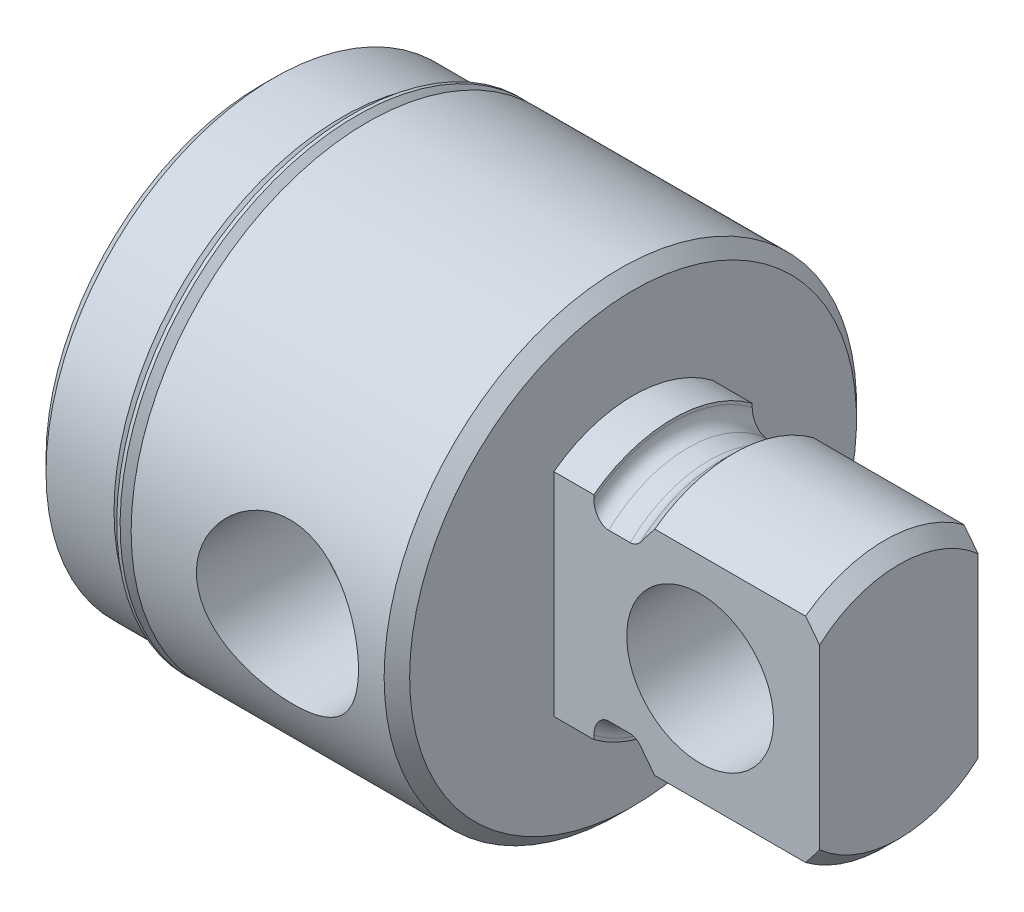
SolidWorks part; units mm, degrees
material "Cast Alloy Steel"
ref_plane "Front Plane" through (0, 0, 0) normal (0, 0, 1) x (1, 0, 0)
ref_plane "Top Plane" through (0, 0, 0) normal (0, 1, 0) x (1, 0, 0)
ref_plane "Right Plane" through (0, 0, 0) normal (1, 0, 0) x (0, 0, -1)
ref_plane "Plane1" through (38.1, 0, 0) normal (1, 0, 0) x (0, 0, -1)
sketch "Sketch1" plane through (0, 0, 0) normal (0, 0, 1) x (1, 0, 0)
  line L0 (0, 0) -> (0, 12.846)
  line L1 (0, 12.846) -> (0.762, 13.6081)
  line L2 (0.762, 13.6081) -> (4.826, 13.6081)
  line L3 (4.826, 13.6081) -> (5.588, 12.846)
  line L4 (5.588, 12.846) -> (6.35, 12.846)
  line L5 (6.35, 12.846) -> (6.35, 14.1097)
  line L6 (6.35, 14.1097) -> (21.463, 14.1097)
  line L7 (21.463, 14.1097) -> (22.225, 13.3477)
  line L8 (22.225, 13.3477) -> (22.225, 0)
  line L9 (22.225, 0) -> (0, 0)
  line L10 (22.225, 0) -> (0, 0) construction
revolve "Revolve1" add sketch "Sketch1" angle 360 about L10 reverse direction yes
sketch "Sketch2" plane through (0, 0, 0) normal (0, 0, 1) x (1, 0, 0)
  line L0 (22.225, 0) -> (22.225, 7.9057)
  line L1 (22.225, 7.9057) -> (24.6126, 7.9057)
  line L2 (24.6126, 7.9057) -> (24.6126, 7.7279)
  line L3 (25.5016, 6.8389) -> (26.7843, 6.8389)
  line L4 (27.383, 7.0708) -> (27.4129, 7.098)
  line L5 (27.4129, 7.098) -> (28.2524, 7.9375)
  line L6 (28.2524, 7.9375) -> (37.2605, 7.9375)
  line L7 (37.2605, 7.9375) -> (38.1, 7.098)
  line L8 (38.1, 7.098) -> (38.1, 0)
  line L9 (38.1, 0) -> (22.225, 0)
  line L10 (38.1, 0) -> (22.225, 0) construction
  arc A0 (24.6126, 7.7279) -> (25.5016, 6.8389) centre (25.5016, 7.7279) ccw
  arc A1 (26.7843, 6.8389) -> (27.383, 7.0708) centre (26.7843, 7.7279) ccw
revolve "Revolve2" add sketch "Sketch2" angle 360 about L10 reverse direction yes
cosmetic thread "Cosmetic Thread1" parameters "D1"=10.6871, "D2"=14.1961
sketch "Sketch3" plane through (38.1, 0, 0) normal (1, 0, 0) x (0, 0, -1)
  line L0 (-28.2194, -56.4388) -> (28.2194, -56.4388)
  line L1 (28.2194, -56.4388) -> (28.2194, 56.4388)
  line L2 (28.2194, 56.4388) -> (-28.2194, 56.4388)
  line L3 (-28.2194, 56.4388) -> (-28.2194, -56.4388)
  line L4 (-4.7307, -28.2194) -> (4.7307, -28.2194)
  line L5 (4.7307, -28.2194) -> (4.7307, 28.2194)
  line L6 (4.7307, 28.2194) -> (-4.7307, 28.2194)
  line L7 (-4.7307, 28.2194) -> (-4.7307, -28.2194)
extrude "Cut-Extrude1" cut sketch "Sketch3" against normal blind 15.875
ref_plane "Plane2" through (22.225, 0, 0) normal (1, 0, 0) x (0, 0, -1)
hole_wizard "Hole1" positions "Sketch5" profile "Sketch4" legacy
sketch "Sketch5" plane through (0, 0, 0) normal (-1, 0, 0) x (0, 0, 1)
  point P0 (0, 0)
sketch "Sketch4" plane through (0, 0, 0) normal (0, 1, 0) x (0, 0, 1)
  line L0 (0, 0) -> (0, 23.7046)
  line L1 (0, 23.7046) -> (4.7625, 20.955)
  line L2 (4.7625, 20.955) -> (4.7625, 0)
  line L4 (4.7625, 0) -> (0, 0)
  line L6 (0, 23.7046) -> (-4.7625, 20.955) construction
  line L7 (0, -4.2442) -> (0, 117.3081) construction
  dimension "Diameter" = 9.525
  dimension "Depth" = 20.955
  dimension "Drill Angle" = 120
ref_plane "Plane3" through (0, 0, 0) normal (0, 0.9998, 0.0175) x (1, 0, 0)
sketch "Sketch6" plane through (0, 0, 0) normal (0, 0.9998, 0.0175) x (1, 0, 0)
  line L0 (15.0876, 0) -> (19.7106, 0)
  line L1 (19.7106, 0) -> (19.7106, -7.1755)
  line L2 (19.7106, -7.1755) -> (19.9271, -14.1097)
  line L3 (19.9271, -14.1097) -> (15.0876, -14.1097)
  line L4 (15.0876, -14.1097) -> (15.0876, 0)
  line L5 (15.0876, -14.1097) -> (15.0876, 0) construction
revolve "Cut-Revolve1" cut sketch "Sketch6" angle 360 about L5 reverse direction yes
cosmetic thread "Cosmetic Thread2" parameters "D1"=6.9342, "D2"=10.287
ref_plane "Plane4" through (15.0876, 0, 0) normal (1, 0, 0) x (0, 0, -1)
ref_plane "Plane5" through (5.588, 0, 0) normal (1, 0, 0) x (0, 0, -1)
sketch "Sketch7" plane through (0, 0, 0) normal (0, 0, 1) x (1, 0, 0)
  line L0 (5.4861, 14.0255) -> (6.2275, 13.2842)
  line L1 (6.2275, 13.1046) -> (5.969, 12.846)
  line L2 (5.969, 12.846) -> (5.588, 12.846)
  line L3 (5.588, 12.846) -> (5.588, 12.592)
  line L4 (5.588, 12.592) -> (6.35, 12.592)
  line L5 (6.35, 12.592) -> (6.35, 13.449)
  line L6 (6.35, 13.449) -> (5.6893, 14.1097)
  line L7 (5.6893, 14.1097) -> (5.4861, 14.1097)
  line L8 (5.4861, 14.1097) -> (5.4861, 14.0255)
  line L9 (6.35, 0) -> (5.588, 0) construction
  arc A0 (6.2275, 13.2842) -> (6.2275, 13.1046) centre (6.1377, 13.1944) cw
revolve "Revolve3" add sketch "Sketch7" angle 360 about L9 reverse direction yes
ref_plane "Plane6" through (38.227, 0, 0) normal (1, 0, 0) x (0, 0, -1)
sketch "Sketch8" plane through (0, 0, 0) normal (0, 0, 1) x (1, 0, 0)
  circle A0 centre (30.9626, 0) radius 4.3878
extrude "Cut-Extrude2" cut sketch "Sketch8" along normal blind 7.0961 and the other way blind 7.0961
ref_plane "Plane7" through (24.6126, 0, 0) normal (1, 0, 0) x (0, 0, -1)
ref_plane "Plane8" through (33.3248, 0, 0) normal (1, 0, 0) x (0, 0, -1)
ref_plane "Plane9" through (30.9626, 0, 0) normal (1, 0, 0) x (0, 0, -1)
ref_plane "Plane10" through (38.1, 0, 0) normal (1, 0, 0) x (0, 0, -1)
ref_plane "Plane11" through (0, 0, 0) normal (0, 0, 1) x (1, 0, 0)
ref_plane "Plane12" through (24.6126, 0, 0) normal (1, 0, 0) x (0, 0, -1)
ref_plane "Plane13" through (0, 0, 0) normal (0, 1, 0) x (1, 0, 0)
ref_plane "Plane14" through (0, 10.2743, 0) normal (0, 1, 0) x (1, 0, 0)
ref_plane "Plane15" through (22.225, 0, 0) normal (1, 0, 0) x (0, 0, -1)
ref_plane "1 XY" through (24.6126, 0, 0) normal (1, 0, 0) x (0, 0, -1)
ref_plane "1 XZ" through (0, 0, 0) normal (0, -1, 0) x (-1, 0, 0)
ref_plane "1 YZ" through (0, 0, 0) normal (0, 0, -1) x (-1, 0, 0)
ref_axis "1 X" through (24.6126, 0, 80.9) along (0, 0, -1)
ref_axis "1 Y" through (24.6126, -50, 0) along (0, 1, 0)
ref_axis "1 Z" through (80.9, 0, 0) along (-1, 0, 0)
sketch3d "1"
  point P0 (24.6126, 0, 0)
ref_plane "c1 XY" through (0, 0, 0) normal (0, 0, 1) x (1, 0, 0)
ref_plane "c1 XZ" through (0, 7.9057, 0) normal (0, -1, 0) x (-1, 0, 0)
ref_plane "c1 YZ" through (22.225, 0, 0) normal (1, 0, 0) x (0, 0, -1)
ref_axis "c1 X" through (-80.9, 7.9057, 0) along (1, 0, 0)
ref_axis "c1 Y" through (22.225, -50, 0) along (0, 1, 0)
ref_axis "c1 Z" through (22.225, 7.9057, 80.9) along (0, 0, -1)
sketch3d "c1"
  point P0 (22.225, 7.9057, 0)
ref_plane "c2 XY" through (0, 0, 0) normal (0, 0, 1) x (1, 0, 0)
ref_plane "c2 XZ" through (0, -7.9057, 0) normal (0, -1, 0) x (-1, 0, 0)
ref_plane "c2 YZ" through (22.225, 0, 0) normal (1, 0, 0) x (0, 0, -1)
ref_axis "c2 X" through (-80.9, -7.9057, 0) along (1, 0, 0)
ref_axis "c2 Y" through (22.225, -50, 0) along (0, 1, 0)
ref_axis "c2 Z" through (22.225, -7.9057, 80.9) along (0, 0, -1)
sketch3d "c2"
  point P0 (22.225, -7.9057, 0)
ref_plane "cc1 XY" through (0, 0, 0) normal (0, 0, 1) x (1, 0, 0)
ref_plane "cc1 XZ" through (0, 0, 0) normal (0, -1, 0) x (-1, 0, 0)
ref_plane "cc1 YZ" through (22.225, 0, 0) normal (1, 0, 0) x (0, 0, -1)
ref_axis "cc1 X" through (-80.9, 0, 0) along (1, 0, 0)
ref_axis "cc1 Y" through (22.225, -50, 0) along (0, 1, 0)
ref_axis "cc1 Z" through (22.225, 0, 80.9) along (0, 0, -1)
sketch3d "cc1"
  point P0 (22.225, 0, 0)
ref_plane "cc2 XY" through (0, 0, 0) normal (0, 0, 1) x (1, 0, 0)
ref_plane "cc2 XZ" through (0, 0, 0) normal (0, -1, 0) x (-1, 0, 0)
ref_plane "cc2 YZ" through (24.6126, 0, 0) normal (1, 0, 0) x (0, 0, -1)
ref_axis "cc2 X" through (-80.9, 0, 0) along (1, 0, 0)
ref_axis "cc2 Y" through (24.6126, -50, 0) along (0, 1, 0)
ref_axis "cc2 Z" through (24.6126, 0, 80.9) along (0, 0, -1)
sketch3d "cc2"
  point P0 (24.6126, 0, 0)
ref_plane "lovra1 XY" through (33.3248, 0, 0) normal (1, 0, 0) x (0, 0, -1)
ref_plane "lovra1 XZ" through (0, 0, 0) normal (0, -1, 0) x (-1, 0, 0)
ref_plane "lovra1 YZ" through (0, 0, 0) normal (0, 0, -1) x (-1, 0, 0)
ref_axis "lovra1 X" through (33.3248, 0, 80.9) along (0, 0, -1)
ref_axis "lovra1 Y" through (33.3248, -50, 0) along (0, 1, 0)
ref_axis "lovra1 Z" through (80.9, 0, 0) along (-1, 0, 0)
sketch3d "lovra1"
  point P0 (33.3248, 0, 0)
ref_plane "lovra2 XY" through (33.3248, 0, 0) normal (1, 0, 0) x (0, 0, -1)
ref_plane "lovra2 XZ" through (0, 11.049, 0) normal (0, -1, 0) x (-1, 0, 0)
ref_plane "lovra2 YZ" through (0, 0, 0) normal (0, 0, -1) x (-1, 0, 0)
ref_axis "lovra2 X" through (33.3248, 11.049, 80.9) along (0, 0, -1)
ref_axis "lovra2 Y" through (33.3248, -50, 0) along (0, 1, 0)
ref_axis "lovra2 Z" through (80.9, 11.049, 0) along (-1, 0, 0)
sketch3d "lovra2"
  point P0 (33.3248, 11.049, 0)
ref_plane "lovra21 XY" through (0, 0, 0) normal (1, 0, 0) x (0, 0, -1)
ref_plane "lovra21 XZ" through (0, 0, 0) normal (0, -1, 0) x (-1, 0, 0)
ref_plane "lovra21 YZ" through (0, 0, 5.2705) normal (0, 0, -1) x (-1, 0, 0)
ref_axis "lovra21 X" through (0, 0, 80.9) along (0, 0, -1)
ref_axis "lovra21 Y" through (0, -50, 5.2705) along (0, 1, 0)
ref_axis "lovra21 Z" through (80.9, 0, 5.2705) along (-1, 0, 0)
sketch3d "lovra21"
  point P0 (0, 0, 5.2705)
ref_plane "lovra22 XY" through (0, 0, 0) normal (1, 0, 0) x (0, 0, -1)
ref_plane "lovra22 XZ" through (0, 0, 0) normal (0, -1, 0) x (-1, 0, 0)
ref_plane "lovra22 YZ" through (0, 0, -5.2705) normal (0, 0, -1) x (-1, 0, 0)
ref_axis "lovra22 X" through (0, 0, 80.9) along (0, 0, -1)
ref_axis "lovra22 Y" through (0, -50, -5.2705) along (0, 1, 0)
ref_axis "lovra22 Z" through (80.9, 0, -5.2705) along (-1, 0, 0)
sketch3d "lovra22"
  point P0 (0, 0, -5.2705)
ref_plane "lovra3 XY" through (33.3248, 0, 0) normal (1, 0, 0) x (0, 0, -1)
ref_plane "lovra3 XZ" through (0, -11.049, 0) normal (0, -1, 0) x (-1, 0, 0)
ref_plane "lovra3 YZ" through (0, 0, 0) normal (0, 0, -1) x (-1, 0, 0)
ref_axis "lovra3 X" through (33.3248, -11.049, 80.9) along (0, 0, -1)
ref_axis "lovra3 Y" through (33.3248, -50, 0) along (0, 1, 0)
ref_axis "lovra3 Z" through (80.9, -11.049, 0) along (-1, 0, 0)
sketch3d "lovra3"
  point P0 (33.3248, -11.049, 0)
ref_plane "olen XY" through (30.9626, 0, 0) normal (1, 0, 0) x (0, 0, -1)
ref_plane "olen XZ" through (0, 0, 0) normal (0, -1, 0) x (-1, 0, 0)
ref_plane "olen YZ" through (0, 0, 0) normal (0, 0, -1) x (-1, 0, 0)
ref_axis "olen X" through (30.9626, 0, 80.9) along (0, 0, -1)
ref_axis "olen Y" through (30.9626, -50, 0) along (0, 1, 0)
ref_axis "olen Z" through (80.9, 0, 0) along (-1, 0, 0)
sketch3d "olen"
  point P0 (30.9626, 0, 0)
ref_plane "p1 XY" through (38.1, 0, 0) normal (1, 0, 0) x (0, 0, -1)
ref_plane "p1 XZ" through (0, 0, 0) normal (0, -1, 0) x (-1, 0, 0)
ref_plane "p1 YZ" through (0, 0, 4.7307) normal (0, 0, -1) x (-1, 0, 0)
ref_axis "p1 X" through (38.1, 0, 80.9) along (0, 0, -1)
ref_axis "p1 Y" through (38.1, -50, 4.7307) along (0, 1, 0)
ref_axis "p1 Z" through (80.9, 0, 4.7307) along (-1, 0, 0)
sketch3d "p1"
  point P0 (38.1, 0, 4.7307)
ref_plane "p2 XY" through (38.1, 0, 0) normal (1, 0, 0) x (0, 0, -1)
ref_plane "p2 XZ" through (0, 0, 0) normal (0, -1, 0) x (-1, 0, 0)
ref_plane "p2 YZ" through (0, 0, -4.7307) normal (0, 0, -1) x (-1, 0, 0)
ref_axis "p2 X" through (38.1, 0, 80.9) along (0, 0, -1)
ref_axis "p2 Y" through (38.1, -50, -4.7307) along (0, 1, 0)
ref_axis "p2 Z" through (80.9, 0, -4.7307) along (-1, 0, 0)
sketch3d "p2"
  point P0 (38.1, 0, -4.7307)
ref_plane "port XY" through (0, 0, 0) normal (0, 0, 1) x (1, 0, 0)
ref_plane "port XZ" through (0, 0, 0) normal (0, -1, 0) x (-1, 0, 0)
ref_plane "port YZ" through (15.0876, 0, 0) normal (1, 0, 0) x (0, 0, -1)
ref_axis "port X" through (-80.9, 0, 0) along (1, 0, 0)
ref_axis "port Y" through (15.0876, -50, 0) along (0, 1, 0)
ref_axis "port Z" through (15.0876, 0, 80.9) along (0, 0, -1)
sketch3d "port"
  point P0 (15.0876, 0, 0)
ref_plane "port2 XY" through (38.1, 0, 0) normal (1, 0, 0) x (0, 0, -1)
ref_plane "port2 XZ" through (0, 0, 0) normal (0, -1, 0) x (-1, 0, 0)
ref_plane "port2 YZ" through (0, 0, 0) normal (0, 0, -1) x (-1, 0, 0)
ref_axis "port2 X" through (38.1, 0, 80.9) along (0, 0, -1)
ref_axis "port2 Y" through (38.1, -50, 0) along (0, 1, 0)
ref_axis "port2 Z" through (80.9, 0, 0) along (-1, 0, 0)
sketch3d "port2"
  point P0 (38.1, 0, 0)
ref_plane "thd1 XY" through (38.1, 0, 0) normal (1, 0, 0) x (0, 0, -1)
ref_plane "thd1 XZ" through (0, 0, 0) normal (0, -1, 0) x (-1, 0, 0)
ref_plane "thd1 YZ" through (0, 0, 7.9375) normal (0, 0, -1) x (-1, 0, 0)
ref_axis "thd1 X" through (38.1, 0, 80.9) along (0, 0, -1)
ref_axis "thd1 Y" through (38.1, -50, 7.9375) along (0, 1, 0)
ref_axis "thd1 Z" through (80.9, 0, 7.9375) along (-1, 0, 0)
sketch3d "thd1"
  point P0 (38.1, 0, 7.9375)
ref_plane "thd2 XY" through (38.1, 0, 0) normal (1, 0, 0) x (0, 0, -1)
ref_plane "thd2 XZ" through (0, 0, 0) normal (0, -1, 0) x (-1, 0, 0)
ref_plane "thd2 YZ" through (0, 0, -7.9375) normal (0, 0, -1) x (-1, 0, 0)
ref_axis "thd2 X" through (38.1, 0, 80.9) along (0, 0, -1)
ref_axis "thd2 Y" through (38.1, -50, -7.9375) along (0, 1, 0)
ref_axis "thd2 Z" through (80.9, 0, -7.9375) along (-1, 0, 0)
sketch3d "thd2"
  point P0 (38.1, 0, -7.9375)
ref_plane "to_mounting_bracket XY" through (22.225, 0, 0) normal (1, 0, 0) x (0, 0, -1)
ref_plane "to_mounting_bracket XZ" through (0, 0, 0) normal (0, -1, 0) x (-1, 0, 0)
ref_plane "to_mounting_bracket YZ" through (0, 0, 0) normal (0, 0, -1) x (-1, 0, 0)
ref_axis "to_mounting_bracket X" through (22.225, 0, 80.9) along (0, 0, -1)
ref_axis "to_mounting_bracket Y" through (22.225, -50, 0) along (0, 1, 0)
ref_axis "to_mounting_bracket Z" through (80.9, 0, 0) along (-1, 0, 0)
sketch3d "to_mounting_bracket"
  point P0 (22.225, 0, 0)
ref_plane "to_nut XY" through (24.6126, 0, 0) normal (1, 0, 0) x (0, 0, -1)
ref_plane "to_nut XZ" through (0, 0, 0) normal (0, -1, 0) x (-1, 0, 0)
ref_plane "to_nut YZ" through (0, 0, 0) normal (0, 0, -1) x (-1, 0, 0)
ref_axis "to_nut X" through (24.6126, 0, 80.9) along (0, 0, -1)
ref_axis "to_nut Y" through (24.6126, -50, 0) along (0, 1, 0)
ref_axis "to_nut Z" through (80.9, 0, 0) along (-1, 0, 0)
sketch3d "to_nut"
  point P0 (24.6126, 0, 0)
ref_plane "to_pin XY" through (0, 0, 0) normal (0, 0, 1) x (1, 0, 0)
ref_plane "to_pin XZ" through (0, 0, 0) normal (0, -1, 0) x (-1, 0, 0)
ref_plane "to_pin YZ" through (30.9626, 0, 0) normal (1, 0, 0) x (0, 0, -1)
ref_axis "to_pin X" through (-80.9, 0, 0) along (1, 0, 0)
ref_axis "to_pin Y" through (30.9626, -50, 0) along (0, 1, 0)
ref_axis "to_pin Z" through (30.9626, 0, 80.9) along (0, 0, -1)
sketch3d "to_pin"
  point P0 (30.9626, 0, 0)
ref_plane "to_screw XY" through (0, 10.2743, 0) normal (0, 1, 0) x (1, 0, 0)
ref_plane "to_screw XZ" through (0, 0, -7.0612) normal (0, 0, 1) x (1, 0, 0)
ref_plane "to_screw YZ" through (15.0876, 0, 0) normal (1, 0, 0) x (0, 0, -1)
ref_axis "to_screw X" through (-80.9, 10.2743, -7.0612) along (1, 0, 0)
ref_axis "to_screw Y" through (15.0876, 10.2743, 50) along (0, 0, -1)
ref_axis "to_screw Z" through (15.0876, 50, -7.0612) along (0, -1, 0)
sketch3d "to_screw"
  point P0 (15.0876, 10.2743, -7.0612)
ref_plane "to_tube XY" through (5.588, 0, 0) normal (1, 0, 0) x (0, 0, -1)
ref_plane "to_tube XZ" through (0, 0, 0) normal (0, -1, 0) x (-1, 0, 0)
ref_plane "to_tube YZ" through (0, 0, 0) normal (0, 0, -1) x (-1, 0, 0)
ref_axis "to_tube X" through (5.588, 0, 80.9) along (0, 0, -1)
ref_axis "to_tube Y" through (5.588, -50, 0) along (0, 1, 0)
ref_axis "to_tube Z" through (80.9, 0, 0) along (-1, 0, 0)
sketch3d "to_tube"
  point P0 (5.588, 0, 0)
